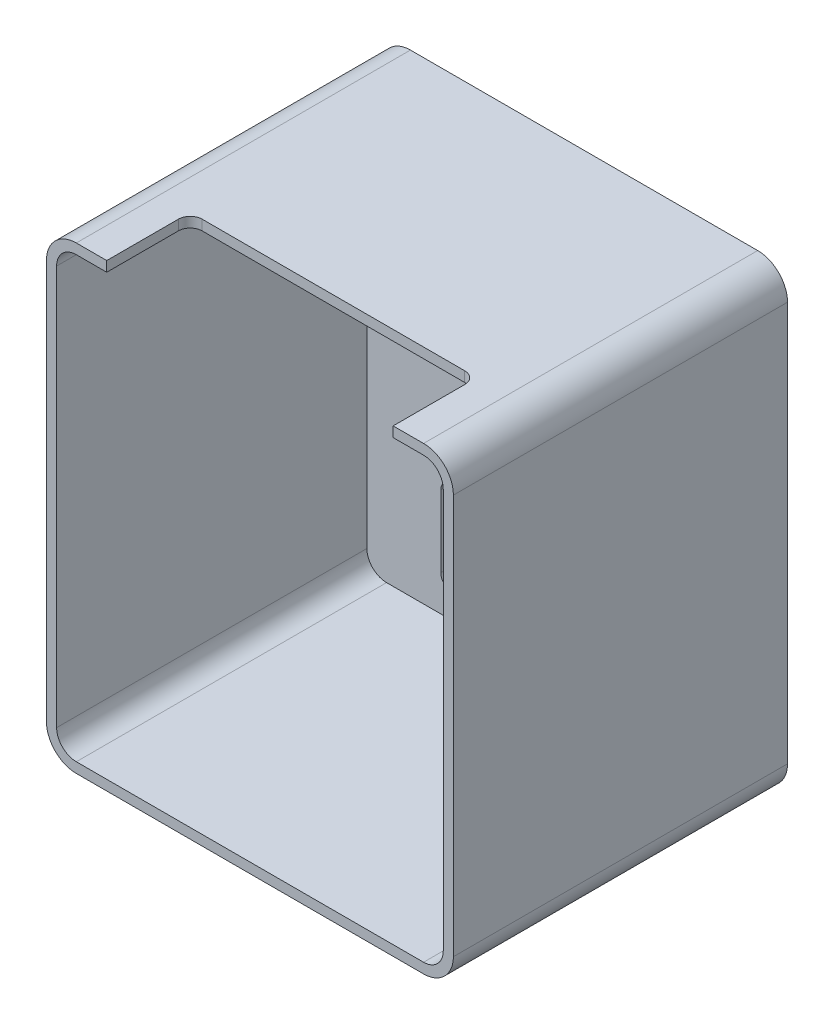
SolidWorks part; units mm, degrees
ref_plane "Front Plane" through (0, 0, 0) normal (0, 0, 1) x (1, 0, 0)
ref_plane "Top Plane" through (0, 0, 0) normal (0, 1, 0) x (1, 0, 0)
ref_plane "Right Plane" through (0, 0, 0) normal (1, 0, 0) x (0, 0, -1)
sketch "Sketch1" plane through (0, 0, 0) normal (0, 0, 1) x (1, 0, 0)
  line L0 (-16.2, -16.75) -> (-16.2, 16.75)
  line L1 (-14.55, -19.25) -> (14.55, -19.25)
  line L2 (-17.05, -16.75) -> (-17.05, 16.75)
  line L3 (-14.55, 19.25) -> (14.55, 19.25)
  line L4 (17.05, -16.75) -> (17.05, 16.75)
  line L5 (-17.05, -19.25) -> (17.05, 19.25) construction
  line L6 (-17.05, 19.25) -> (17.05, -19.25) construction
  line L7 (-14.55, 18.4) -> (14.55, 18.4)
  line L8 (16.2, -16.75) -> (16.2, 16.75)
  line L9 (-14.55, -18.4) -> (14.55, -18.4)
  line L15 (0, 0) -> (0, -19.25) construction
  line L16 (-9, -16.4) -> (9, -16.4)
  line L17 (-10, -15.4) -> (-10, -9.4)
  line L18 (-9, -8.4) -> (9, -8.4)
  line L19 (10, -15.4) -> (10, -9.4)
  line L20 (-10, -16.4) -> (10, -8.4) construction
  line L21 (-10, -8.4) -> (10, -16.4) construction
  arc A0 (-14.55, -19.25) -> (-17.05, -16.75) centre (-14.55, -16.75) cw
  arc A1 (14.55, -19.25) -> (17.05, -16.75) centre (14.55, -16.75) ccw
  arc A2 (14.55, 19.25) -> (17.05, 16.75) centre (14.55, 16.75) cw
  arc A3 (-17.05, 16.75) -> (-14.55, 19.25) centre (-14.55, 16.75) cw
  arc A4 (-16.2, 16.75) -> (-14.55, 18.4) centre (-14.55, 16.75) cw
  arc A5 (14.55, 18.4) -> (16.2, 16.75) centre (14.55, 16.75) cw
  arc A6 (14.55, -18.4) -> (16.2, -16.75) centre (14.55, -16.75) ccw
  arc A7 (-14.55, -18.4) -> (-16.2, -16.75) centre (-14.55, -16.75) cw
  arc A12 (9, -8.4) -> (10, -9.4) centre (9, -9.4) cw
  arc A13 (9, -16.4) -> (10, -15.4) centre (9, -15.4) ccw
  arc A14 (-9, -16.4) -> (-10, -15.4) centre (-9, -15.4) cw
  arc A15 (-10, -9.4) -> (-9, -8.4) centre (-9, -9.4) cw
  point P0 (0, 0)
  point P42 (0, -12.4)
  point P61 (0, -10.1003)
  dimension "D3" = 2.5
  dimension "D6" = 1
  dimension "D1" = 34.1
  dimension "D2" = 38.5
  dimension "D7" = 8
  dimension "D5" = 2
  dimension "D8" = 20
  dimension "D4" = 0.85
extrude "Boss-Extrude1" add sketch "Sketch1" along normal blind 28 contours A3 L2 A0 L1 A1 L4 A2 L3 L9 A7 L0 A4 L7 A5 L8 A6 region at (-15.9541, -18.1541, 0)
extrude "Boss-Extrude2" add sketch "Sketch1<3>" along normal blind 2 contours A7 L9 A6 L8 A5 L7 A4 L0 L17 A15 L18 A12 L19 A13 L16 A14 region at (0, 1.9143, 0)
sketch "Sketch1<3>" plane through (0, 0, 0) normal (0, 0, 1) x (1, 0, 0) same geometry as "Sketch1"
sketch "Sketch2" plane through (0, 0, 0) normal (0, 1, 0) x (1, 0, 0)
  line L0 (-14.55, -28) -> (14.55, -28) construction
  line L1 (-12, -28) -> (12, -28)
  line L2 (-12, -28) -> (-12, -22)
  line L3 (-11, -21) -> (11, -21)
  line L4 (12, -28) -> (12, -22)
  line L5 (0, 0) -> (0, -28) construction
  arc A0 (11, -21) -> (12, -22) centre (11, -22) cw
  arc A1 (-12, -22) -> (-11, -21) centre (-11, -22) cw
  point P9 (0, -28)
  dimension "D1" = 1
  dimension "D2" = 24
  dimension "D3" = 7
extrude "Cut-Extrude1" cut sketch "Sketch2" along normal through all contours L2 A1 L3 A0 L4 L1
